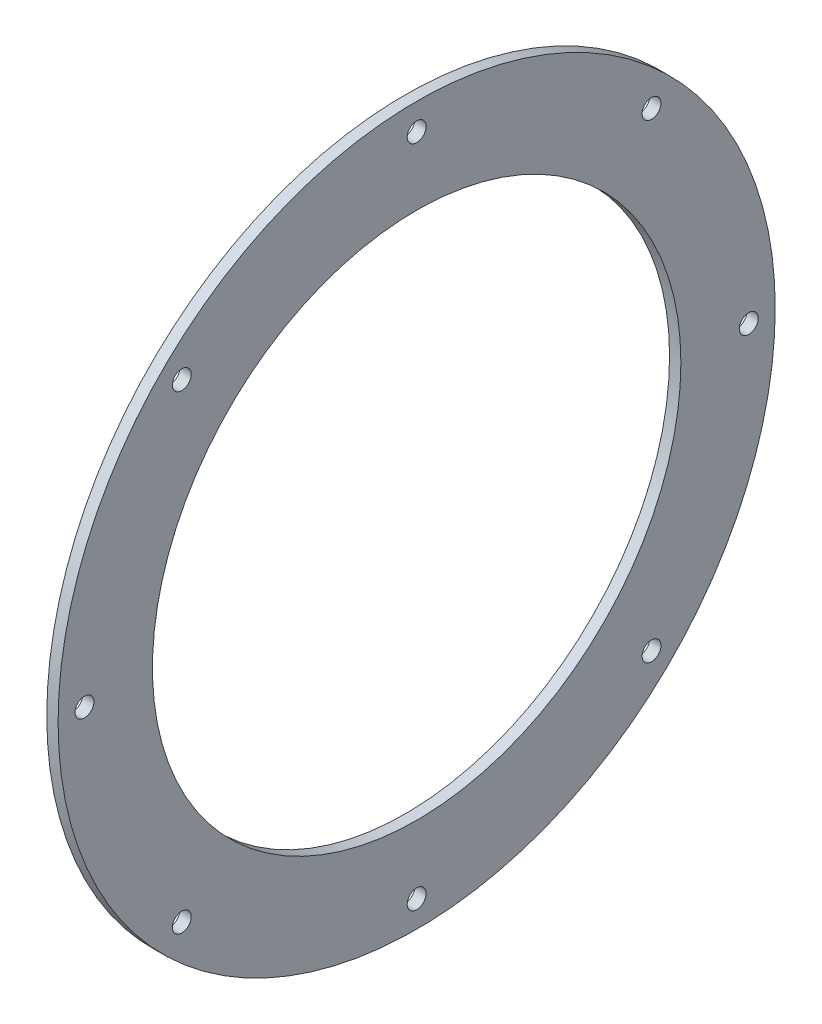
SolidWorks part; units mm, degrees
material "201 Stal nierdzewna odprężona (SS)"
ref_plane "Płaszczyzna przednia" through (0, 0, 0) normal (0, 0, 1) x (1, 0, 0)
ref_plane "Płaszczyzna górna" through (0, 0, 0) normal (0, 1, 0) x (1, 0, 0)
ref_plane "Płaszczyzna prawa" through (0, 0, 0) normal (1, 0, 0) x (0, 0, -1)
sketch "Szkic1" plane through (0, 0, 0) normal (1, 0, 0) x (0, 0, -1)
  circle A0 centre (0, 0) radius 95
  circle A1 centre (0, 0) radius 70
  circle A2 centre (0, 88) radius 2.5
  circle A3 centre (62.2254, 62.2254) radius 2.5
  circle A4 centre (88, 0) radius 2.5
  circle A5 centre (62.2254, -62.2254) radius 2.5
  circle A6 centre (0, -88) radius 2.5
  circle A7 centre (-62.2254, -62.2254) radius 2.5
  circle A8 centre (-88, 0) radius 2.5
  circle A9 centre (-62.2254, 62.2254) radius 2.5
  point P22 (0, 0)
  dimension "D1" = 190
  dimension "D2" = 140
  dimension "D4" = 5
  dimension "D3" = 88
  dimension "D5" = 8
extrude "Dodanie-wyciągnięcie1" add sketch "Szkic1" along normal blind 3
